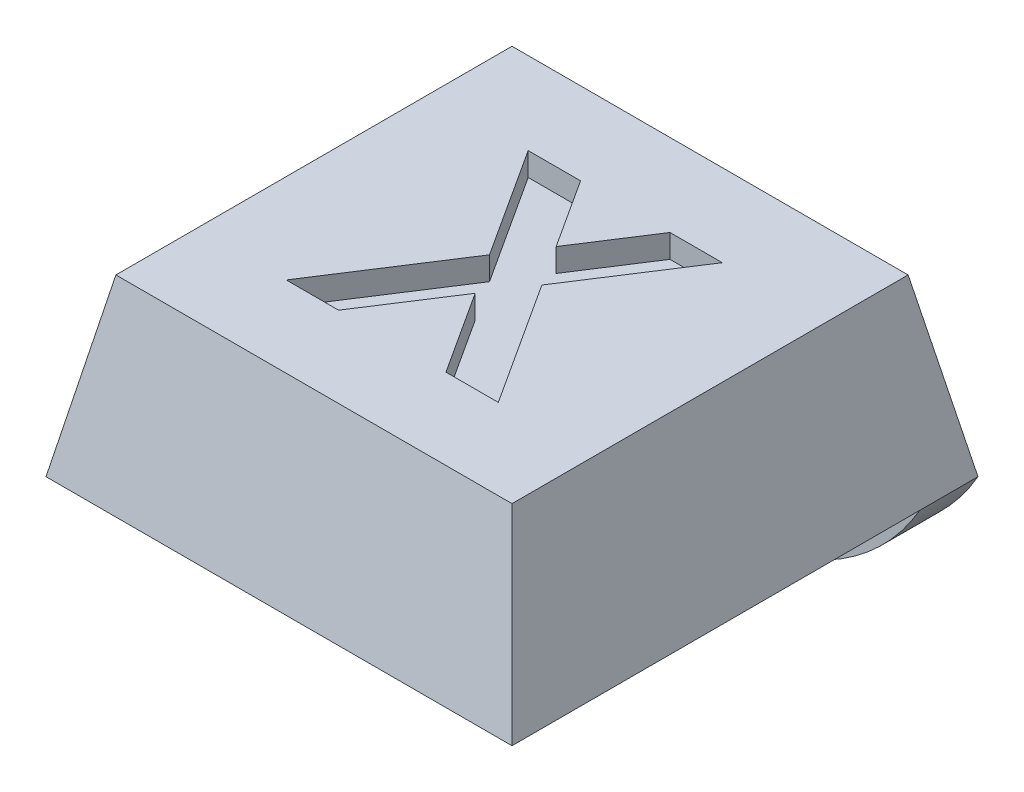
SolidWorks part; units mm, degrees
ref_plane "Front Plane" through (0, 0, 0) normal (0, 0, 1) x (1, 0, 0)
ref_plane "Top Plane" through (0, 0, 0) normal (0, 1, 0) x (1, 0, 0)
ref_plane "Right Plane" through (0, 0, 0) normal (1, 0, 0) x (0, 0, -1)
sketch "Sketch1" plane through (0, 0, 0) normal (0, 1, 0) x (1, 0, 0)
  line L1 (0, 0) -> (8, 0)
  line L2 (0, 0) -> (0, 8)
  line L3 (0, 8) -> (8, 8)
  line L4 (8, 0) -> (8, 8)
  dimension "D1" = 8
  dimension "D2" = 8
extrude "Boss-Extrude1" add sketch "Sketch1" along normal blind 3
sketch "Sketch2" plane through (0, 0, 0) normal (0, 0, 1) x (1, 0, 0)
  line L0 (0, 0) -> (0.6, 3)
  line L1 (0, 3) -> (8, 3) construction
  line L2 (0.6, 3) -> (0, 3)
  line L3 (0, 3) -> (0, 0)
  line L4 (8, 0) -> (7.4, 3)
  line L5 (7.4, 3) -> (8, 3)
  line L6 (8, 3) -> (8, 0)
  dimension "D1" = 0.6
  dimension "D2" = 0.6
extrude "Cut-Extrude1" cut sketch "Sketch2" against normal through all both and the other way through all
sketch "Sketch3" plane through (0, 0, 0) normal (1, 0, 0) x (0, 0, -1)
  line L0 (0, 0) -> (0.6, 3)
  line L1 (8, 3) -> (0, 3) construction
  line L2 (0.6, 3) -> (0, 3)
  line L3 (0, 3) -> (0, 0)
  line L4 (8, 3) -> (7.4, 3)
  line L5 (7.4, 3) -> (8, 0)
  line L6 (8, 3) -> (8, 0)
  dimension "D1" = 0.6
  dimension "D2" = 0.6
extrude "Cut-Extrude2" cut sketch "Sketch3" along normal blind 11
sketch "Sketch4" plane through (0, 0, 0) normal (0, -1, 0) x (1, 0, 0)
  line L0 (8, 0) -> (8, -8) construction
  line L3 (0, 0) -> (8, 0) construction
  circle A0 centre (4, -3.75) radius 1.75
  dimension "D1" = 3.5
  dimension "D2" = 4
  dimension "D3" = 3.75
extrude "Cut-Extrude3" cut sketch "Sketch4" against normal blind 0.4
sketch "Sketch5" plane through (0, 0, 0) normal (0, -1, 0) x (1, 0, 0)
  line L0 (8, 0) -> (8, -8) construction
  line L1 (0, -8) -> (8, -8)
  line L2 (0, -8) -> (0, -7)
  line L3 (0, -7) -> (8, -7)
  line L4 (8, -8) -> (8, -7)
  dimension "D1" = 1
extrude "Boss-Extrude2" add sketch "Sketch5" along normal blind 2
fillet "Fillet1" radius 4 2 edges at (8, -2, -7.5) (0, -2, -7.5)
sketch "Sketch6" plane through (0, 3, 0) normal (0, 1, 0) x (1, 0, 0)
  text T0 "X" font "Arial" height 4
extrude "Cut-Extrude4" cut sketch "Sketch6" against normal blind 0.4
